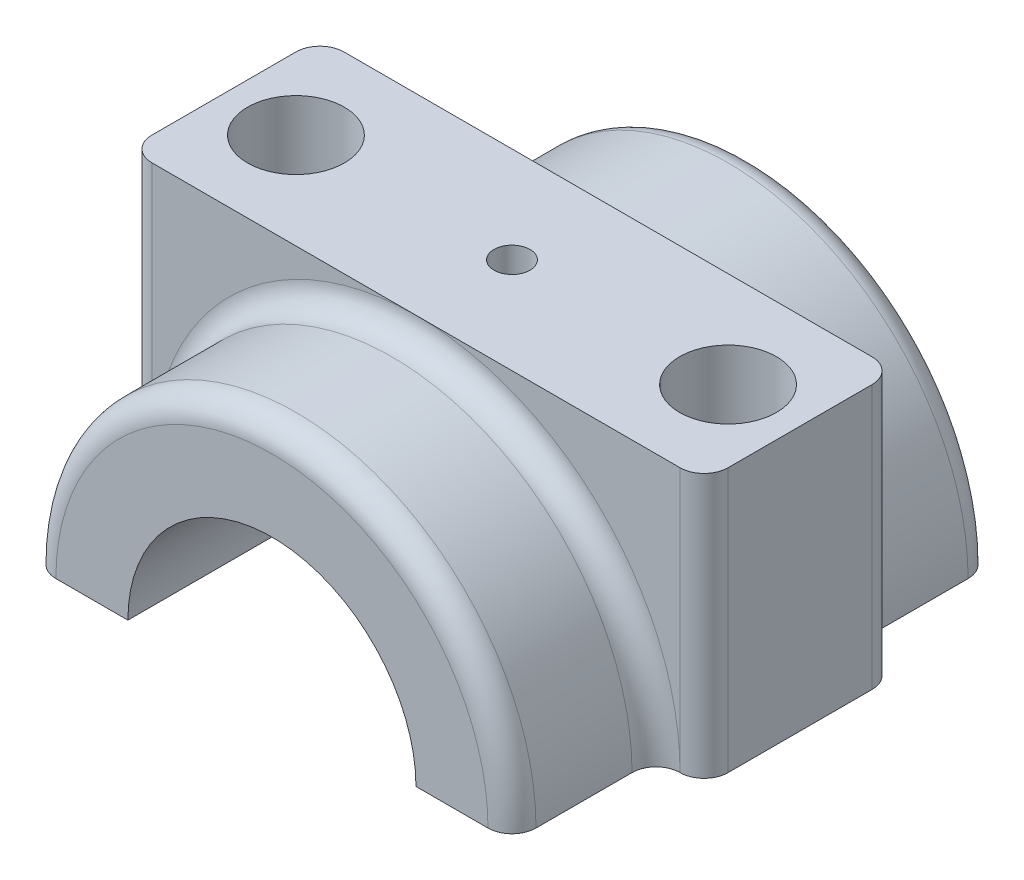
SolidWorks part; units mm, degrees
ref_plane "前基準面" through (0, 0, 0) normal (0, 0, 1) x (1, 0, 0)
ref_plane "上基準面" through (0, 0, 0) normal (0, 1, 0) x (1, 0, 0)
ref_plane "右基準面" through (0, 0, 0) normal (1, 0, 0) x (0, 0, -1)
sketch "草圖2" plane through (0, 0, 0) normal (0, 1, 0) x (1, 0, 0)
  line L0 (0, 0) -> (72, 0)
  line L1 (72, 0) -> (72, 24)
  line L2 (72, 24) -> (0, 24)
  line L3 (0, 24) -> (0, 0)
  line L4 (36, 0) -> (36, 39.469) construction
  line L5 (0, 12) -> (79.7794, 12) construction
  circle A0 centre (9, 12) radius 6.05
  circle A1 centre (63, 12) radius 6.05
  circle A2 centre (36, 12) radius 2.25
  dimension "D1" = 4.5
  dimension "D2" = 12.1
  dimension "D3" = 12.1
  dimension "D4" = 24
  dimension "D5" = 72
  dimension "D6" = 27
extrude "填料-伸長1" add sketch "草圖2" along normal blind 33
fillet "圓角1" radius 3 4 edges at (0, 16.5, 0) (0, 16.5, -24) (72, 16.5, -24) (72, 16.5, 0)
sketch "草圖4" plane through (0, 0, 0) normal (0, 0, 1) x (1, 0, 0)
  line L0 (3, 0) -> (69, 0) construction
  line L1 (6, 0) -> (66, 0)
  arc A0 (54, 0) -> (18, 0) centre (36, 0) ccw
  arc A1 (66, 0) -> (6, 0) centre (36, 0) ccw
  line M3 (3, 0) -> (69, 0)
  dimension "D1" = 18
  dimension "D2" = 30
extrude "填料-伸長2" add sketch "草圖4" along normal blind 18 contours A1 A0 M3 region at (36, 29.3292, 0)
sketch "草圖5" plane through (0, 0, -24) normal (0, 0, -1) x (-1, 0, 0)
  line L0 (-69, 0) -> (-3, 0) construction
  line L1 (-66, 0) -> (-6, 0)
  arc A0 (-18, 0) -> (-54, 0) centre (-36, 0) ccw
  arc A1 (-6, 0) -> (-66, 0) centre (-36, 0) ccw
  line M1 (-69, 0) -> (-3, 0)
  dimension "D1" = 18
extrude "填料-伸長3" add sketch "草圖5" along normal blind 18 contours A1 A0 M1 region at (36, 29.3292, -24)
fillet "圓角2" radius 3 4 edges at (36, 30, -42) (36, 30, -24) (36, 30, 18) (36, 30, 0)
